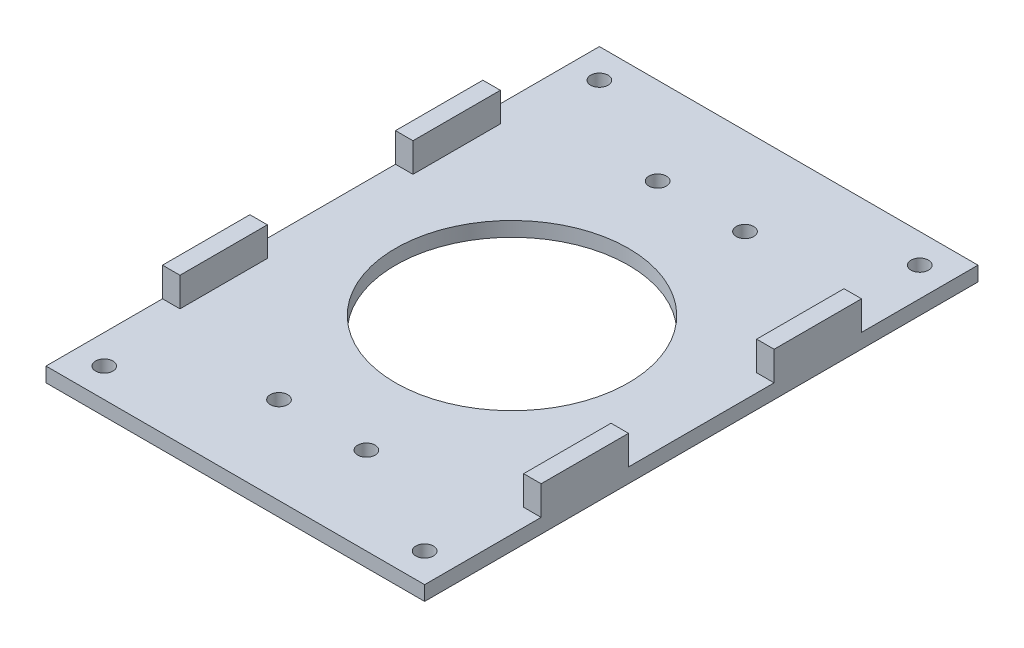
SolidWorks part; units mm, degrees
material "PET"
ref_plane "Alzado" through (0, 0, 0) normal (0, 0, 1) x (1, 0, 0)
ref_plane "Planta" through (0, 0, 0) normal (0, 1, 0) x (1, 0, 0)
ref_plane "Vista lateral" through (0, 0, 0) normal (1, 0, 0) x (0, 0, -1)
sketch "Croquis1" plane through (0, 0, 0) normal (0, 1, 0) x (1, 0, 0)
  line L1 (-32.5, -47.5) -> (32.5, -47.5)
  line L2 (-32.5, -47.5) -> (-32.5, 47.5)
  line L3 (-32.5, 47.5) -> (32.5, 47.5)
  line L4 (32.5, -47.5) -> (32.5, 47.5)
  line L5 (-32.5, -47.5) -> (32.5, 47.5) construction
  line L6 (-32.5, 47.5) -> (32.5, -47.5) construction
  point P0 (0, 0)
  dimension "D1" = 95
  dimension "D2" = 65
extrude "Saliente-Extruir1" add sketch "Croquis1" along normal blind 2.5
sketch "Croquis2" plane through (0, 2.5, 0) normal (0, 1, 0) x (1, 0, 0)
  line L0 (-32.5, 47.5) -> (-32.5, -47.5) construction
  line L1 (-32.5, 27.5) -> (-29.5, 27.5)
  line L2 (-32.5, 27.5) -> (-32.5, 12.5)
  line L3 (-32.5, 12.5) -> (-29.5, 12.5)
  line L4 (-29.5, 27.5) -> (-29.5, 12.5)
  line L5 (32.5, 47.5) -> (-32.5, 47.5) construction
  line L11 (-1.375, 0) -> (1.375, 0) construction
  line L12 (-32.5, -12.5) -> (-29.5, -12.5)
  line L13 (-29.5, -27.5) -> (-29.5, -12.5)
  line L14 (-32.5, -27.5) -> (-29.5, -27.5)
  line L15 (-32.5, -27.5) -> (-32.5, -12.5)
  line L16 (0, -1.375) -> (0, 1.375) construction
  line L17 (32.5, 12.5) -> (29.5, 12.5)
  line L18 (29.5, 27.5) -> (29.5, 12.5)
  line L19 (32.5, 27.5) -> (29.5, 27.5)
  line L20 (32.5, 27.5) -> (32.5, 12.5)
  line L21 (32.5, -27.5) -> (32.5, -12.5)
  line L22 (32.5, -27.5) -> (29.5, -27.5)
  line L23 (29.5, -27.5) -> (29.5, -12.5)
  line L24 (32.5, -12.5) -> (29.5, -12.5)
  dimension "D1" = 3
  dimension "D2" = 15
  dimension "D3" = 20
extrude "Saliente-Extruir2" add sketch "Croquis2" along normal blind 5
sketch "Croquis3" plane through (0, 2.5, 0) normal (0, 1, 0) x (1, 0, 0)
  line L0 (32.5, 47.5) -> (-32.5, 47.5) construction
  line L1 (32.5, 27.5) -> (32.5, 47.5) construction
  line L2 (-4.125, 0) -> (4.125, 0) construction
  line L3 (0, -4.125) -> (0, 4.125) construction
  circle A0 centre (27.5, 42.5) radius 1.5
  circle A1 centre (7.5, 32.5) radius 1.5
  circle A2 centre (7.5, -32.5) radius 1.5
  circle A3 centre (27.5, -42.5) radius 1.5
  circle A4 centre (-27.5, 42.5) radius 1.5
  circle A5 centre (-7.5, 32.5) radius 1.5
  circle A6 centre (-27.5, -42.5) radius 1.5
  circle A7 centre (-7.5, -32.5) radius 1.5
  dimension "D1" = 3
  dimension "D4" = 3
  dimension "D2" = 5
  dimension "D3" = 5
  dimension "D5" = 25
  dimension "D6" = 15
extrude "Cortar-Extruir2" cut sketch "Croquis3" against normal through all
sketch "Croquis4" plane through (0, 2.5, 0) normal (0, 1, 0) x (1, 0, 0)
  circle A0 centre (0, 0) radius 20
  dimension "D1" = 40
extrude "Cortar-Extruir3" cut sketch "Croquis4" against normal through all
